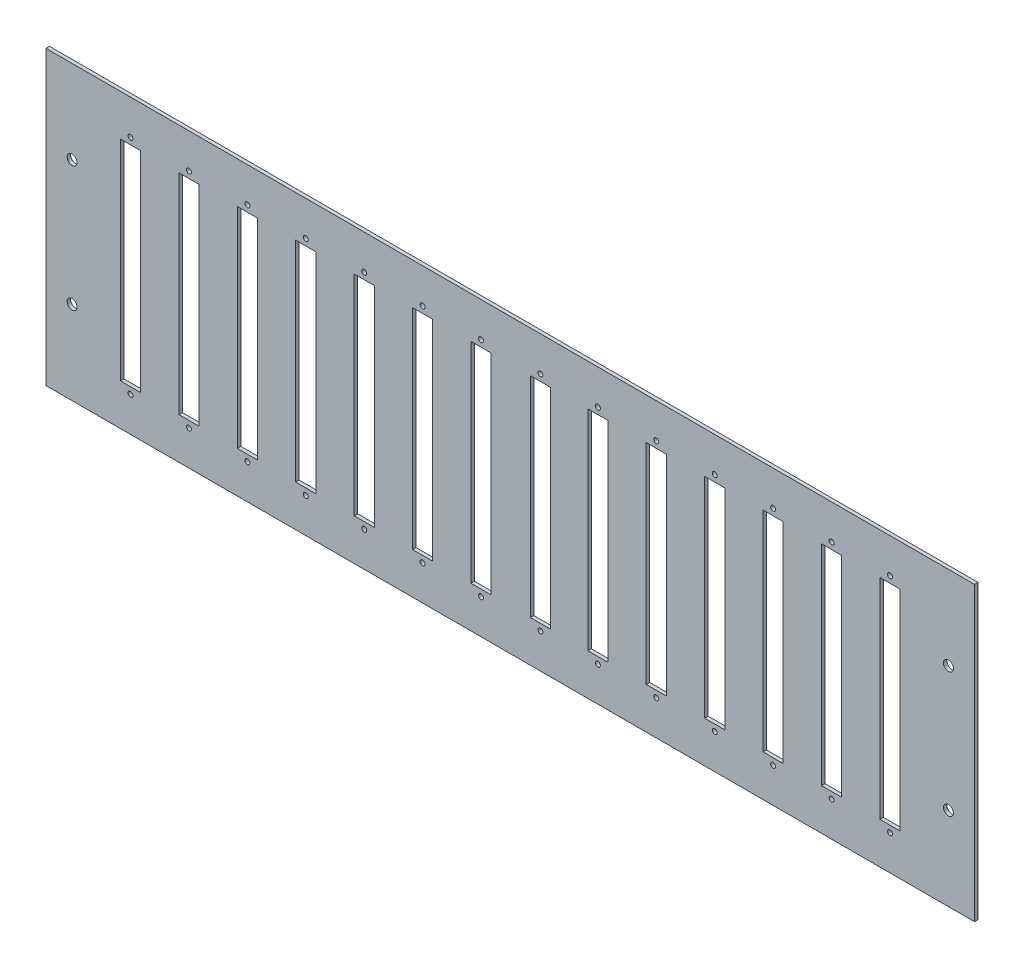
SolidWorks part; units mm, degrees
ref_plane "Front Plane" through (0, 0, 0) normal (0, 0, 1) x (1, 0, 0)
ref_plane "Top Plane" through (0, 0, 0) normal (0, 1, 0) x (1, 0, 0)
ref_plane "Right Plane" through (0, 0, 0) normal (1, 0, 0) x (0, 0, -1)
sketch "Sketch1" plane through (0, 0, 0) normal (0, 0, 1) x (1, 0, 0)
  line L0 (0, 114.4905) -> (423.8752, 114.4905) construction
  line L5 (0, 0) -> (423.8752, 0)
  line L6 (0, 0) -> (0, 133.35)
  line L7 (0, 133.35) -> (423.8752, 133.35)
  line L8 (423.8752, 0) -> (423.8752, 133.35)
  line L9 (33.9789, 114.4905) -> (43.1863, 114.4905)
  line L10 (33.9789, 114.4905) -> (33.9788, 18.8595)
  line L11 (33.9788, 18.8595) -> (43.1864, 18.8595)
  line L12 (43.1863, 114.4905) -> (43.1864, 18.8595)
  line L13 (0, 18.8595) -> (423.8752, 18.8595) construction
  line L14 (38.5826, 133.35) -> (38.5826, 0) construction
  line L15 (65.2526, 133.35) -> (65.2526, 0) construction
  line L16 (91.9226, 133.35) -> (91.9226, 0) construction
  line L17 (118.5926, 133.35) -> (118.5926, 0) construction
  line L18 (145.2626, 133.35) -> (145.2626, 0) construction
  line L19 (198.6026, 133.35) -> (198.6026, 0) construction
  line L20 (171.9326, 133.35) -> (171.9326, 0) construction
  line L21 (225.7042, 133.35) -> (225.7042, 0) construction
  line L22 (251.9426, 133.35) -> (251.9426, 0) construction
  line L23 (278.6126, 133.35) -> (278.6126, 0) construction
  line L24 (305.2826, 133.35) -> (305.2826, 0) construction
  line L25 (331.9526, 133.35) -> (331.9526, 0) construction
  line L26 (385.2926, 133.35) -> (385.2926, 0) construction
  line L27 (358.6226, 133.35) -> (358.6226, 0) construction
  line L28 (0, 15.875) -> (423.8752, 15.875) construction
  line L29 (0, 117.475) -> (423.8752, 117.475) construction
  line L30 (60.6488, 114.4905) -> (69.8563, 114.4905)
  line L31 (60.6488, 114.4905) -> (60.6488, 18.8595)
  line L32 (60.6488, 18.8595) -> (69.8564, 18.8595)
  line L33 (69.8563, 114.4905) -> (69.8564, 18.8595)
  line L34 (87.3188, 114.4905) -> (96.5263, 114.4905)
  line L35 (87.3188, 114.4905) -> (87.3188, 18.8595)
  line L36 (87.3188, 18.8595) -> (96.5264, 18.8595)
  line L37 (96.5263, 114.4905) -> (96.5264, 18.8595)
  line L38 (113.9888, 114.4905) -> (123.1963, 114.4905)
  line L39 (113.9888, 114.4905) -> (113.9888, 18.8595)
  line L40 (113.9888, 18.8595) -> (123.1964, 18.8595)
  line L41 (123.1963, 114.4905) -> (123.1964, 18.8595)
  line L42 (140.6589, 114.4905) -> (149.8663, 114.4905)
  line L43 (140.6589, 114.4905) -> (140.6589, 18.8595)
  line L44 (140.6589, 18.8595) -> (149.8663, 18.8595)
  line L45 (149.8663, 114.4905) -> (149.8663, 18.8595)
  line L46 (247.3389, 114.4905) -> (256.5464, 114.4905)
  line L47 (247.3389, 114.4905) -> (247.3389, 18.8595)
  line L48 (247.3389, 18.8595) -> (256.5464, 18.8595)
  line L49 (256.5464, 114.4905) -> (256.5464, 18.8595)
  line L50 (167.3288, 114.4905) -> (176.5363, 114.4905)
  line L51 (167.3288, 114.4905) -> (167.3288, 18.8595)
  line L52 (167.3288, 18.8595) -> (176.5363, 18.8595)
  line L53 (176.5363, 114.4905) -> (176.5363, 18.8595)
  line L54 (193.9989, 114.4905) -> (203.2063, 114.4905)
  line L55 (193.9989, 114.4905) -> (193.9989, 18.8595)
  line L56 (193.9989, 18.8595) -> (203.2063, 18.8595)
  line L57 (203.2063, 114.4905) -> (203.2063, 18.8595)
  line L58 (221.1004, 114.4905) -> (230.3079, 114.4905)
  line L59 (221.1004, 114.4905) -> (221.1004, 18.8595)
  line L60 (221.1004, 18.8595) -> (230.3079, 18.8595)
  line L61 (230.3079, 114.4905) -> (230.3079, 18.8595)
  line L62 (274.0088, 114.4905) -> (283.2163, 114.4905)
  line L63 (274.0088, 114.4905) -> (274.0088, 18.8595)
  line L64 (274.0088, 18.8595) -> (283.2163, 18.8595)
  line L65 (283.2163, 114.4905) -> (283.2163, 18.8595)
  line L66 (300.6788, 114.4905) -> (309.8863, 114.4905)
  line L67 (300.6788, 114.4905) -> (300.6788, 18.8595)
  line L92 (300.6788, 18.8595) -> (309.8863, 18.8595)
  line L93 (309.8863, 114.4905) -> (309.8863, 18.8595)
  line L94 (327.3488, 114.4905) -> (336.5563, 114.4905)
  line L95 (327.3488, 114.4905) -> (327.3488, 18.8595)
  line L96 (327.3488, 18.8595) -> (336.5563, 18.8595)
  line L97 (336.5563, 114.4905) -> (336.5563, 18.8595)
  line L98 (354.0188, 114.4905) -> (363.2263, 114.4905)
  line L99 (354.0188, 114.4905) -> (354.0188, 18.8595)
  line L100 (354.0188, 18.8595) -> (363.2263, 18.8595)
  line L101 (363.2263, 114.4905) -> (363.2263, 18.8595)
  line L102 (380.6888, 114.4905) -> (389.8963, 114.4905)
  line L103 (380.6888, 114.4905) -> (380.6888, 18.8595)
  line L104 (380.6888, 18.8595) -> (389.8963, 18.8595)
  line L105 (389.8963, 114.4905) -> (389.8963, 18.8595)
  circle A0 centre (11.9126, 38.1) radius 2.2606
  circle A1 centre (11.9126, 95.25) radius 2.2606
  circle A2 centre (411.9626, 95.25) radius 2.2606
  circle A3 centre (411.9626, 38.1) radius 2.2606
  circle A4 centre (38.5826, 117.475) radius 1.1303
  circle A5 centre (38.5826, 15.875) radius 1.1303
  circle A6 centre (65.2526, 117.475) radius 1.1303
  circle A7 centre (65.2526, 15.875) radius 1.1303
  circle A8 centre (91.9226, 117.475) radius 1.1303
  circle A9 centre (91.9226, 15.875) radius 1.1303
  circle A10 centre (118.5926, 117.475) radius 1.1303
  circle A11 centre (118.5926, 15.875) radius 1.1303
  circle A12 centre (145.2626, 117.475) radius 1.1303
  circle A13 centre (145.2626, 15.875) radius 1.1303
  circle A14 centre (171.9326, 117.475) radius 1.1303
  circle A15 centre (171.9326, 15.875) radius 1.1303
  circle A16 centre (198.6026, 117.475) radius 1.1303
  circle A17 centre (198.6026, 15.875) radius 1.1303
  circle A18 centre (225.7042, 117.475) radius 1.1303
  circle A19 centre (225.7042, 15.875) radius 1.1303
  circle A32 centre (251.9426, 117.475) radius 1.1303
  circle A33 centre (251.9426, 15.875) radius 1.1303
  circle A34 centre (278.6126, 117.475) radius 1.1303
  circle A35 centre (278.6126, 15.875) radius 1.1303
  circle A36 centre (305.2826, 117.475) radius 1.1303
  circle A37 centre (305.2826, 15.875) radius 1.1303
  circle A38 centre (331.9526, 117.475) radius 1.1303
  circle A39 centre (331.9526, 15.875) radius 1.1303
  circle A40 centre (358.6226, 117.475) radius 1.1303
  circle A41 centre (358.6226, 15.875) radius 1.1303
  circle A42 centre (385.2926, 117.475) radius 1.1303
  circle A43 centre (385.2926, 15.875) radius 1.1303
  point P61 (38.5826, 114.4905)
  point P64 (65.2526, 114.4905)
  point P65 (65.2526, 18.8595)
  point P82 (91.9226, 114.4905)
  point P85 (118.5926, 114.4905)
  point P86 (118.5926, 18.8595)
  point P87 (91.9226, 18.8595)
  point P96 (198.6026, 114.4905)
  point P97 (0, 0)
  point P110 (145.2626, 114.4905)
  point P113 (171.9326, 114.4905)
  point P114 (171.9326, 18.8595)
  point P132 (225.7042, 114.4905)
  point P133 (225.7042, 18.8595)
  point P134 (198.6026, 18.8595)
  point P145 (0, 0)
  point P146 (251.9426, 114.4905)
  point P149 (278.6126, 114.4905)
  point P150 (305.2826, 114.4905)
  point P151 (331.9526, 114.4905)
  point P152 (358.6226, 114.4905)
  point P153 (385.2926, 114.4905)
  point P154 (115.3014, 50.7934)
  point P155 (385.2926, 18.8595)
  point P156 (358.6226, 18.8595)
  point P157 (0, 0)
  point P158 (0, 0)
  point P159 (331.9526, 18.8595)
  point P160 (305.2826, 18.8595)
  point P162 (278.6126, 18.8595)
  point P163 (251.9426, 18.8595)
  point P167 (145.2626, 18.8595)
  point P168 (0, 0)
  point P169 (0, 0)
  point P170 (0, 0)
  point P224 (0, 0)
  point P225 (0, 0)
  dimension "D3" = 18.8595
  dimension "D7" = 2.2606
  dimension "D8" = 2.2606
  dimension "D1" = 400.05
  dimension "D2" = 18.8595
  dimension "D4" = 9.2075
  dimension "D5" = 15.875
  dimension "D6" = 15.875
  dimension "D9" = 9.2075
  dimension "D10" = 9.2075
  dimension "D11" = 9.2075
  dimension "D12" = 9.2075
  dimension "D13" = 9.2075
  dimension "D14" = 9.2075
  dimension "D15" = 9.2075
  dimension "D16" = 9.2075
  dimension "D22" = 9.2075
  dimension "D23" = 9.2075
  dimension "D24" = 9.2075
  dimension "D26" = 9.2075
  dimension "D27" = 9.2075
extrude "Boss-Extrude1" add sketch "Sketch1" along normal blind 1.5875 contours L5 L8 L7 L6 A43 L104 L103 L102 L105 A42 A41 A40 A39 A38 A37 A36 A35 A34 A33 A32 A19 A18 A17 A16 A15 A14 A13 A12 A11 region at (211.9289, 66.675, 0)
